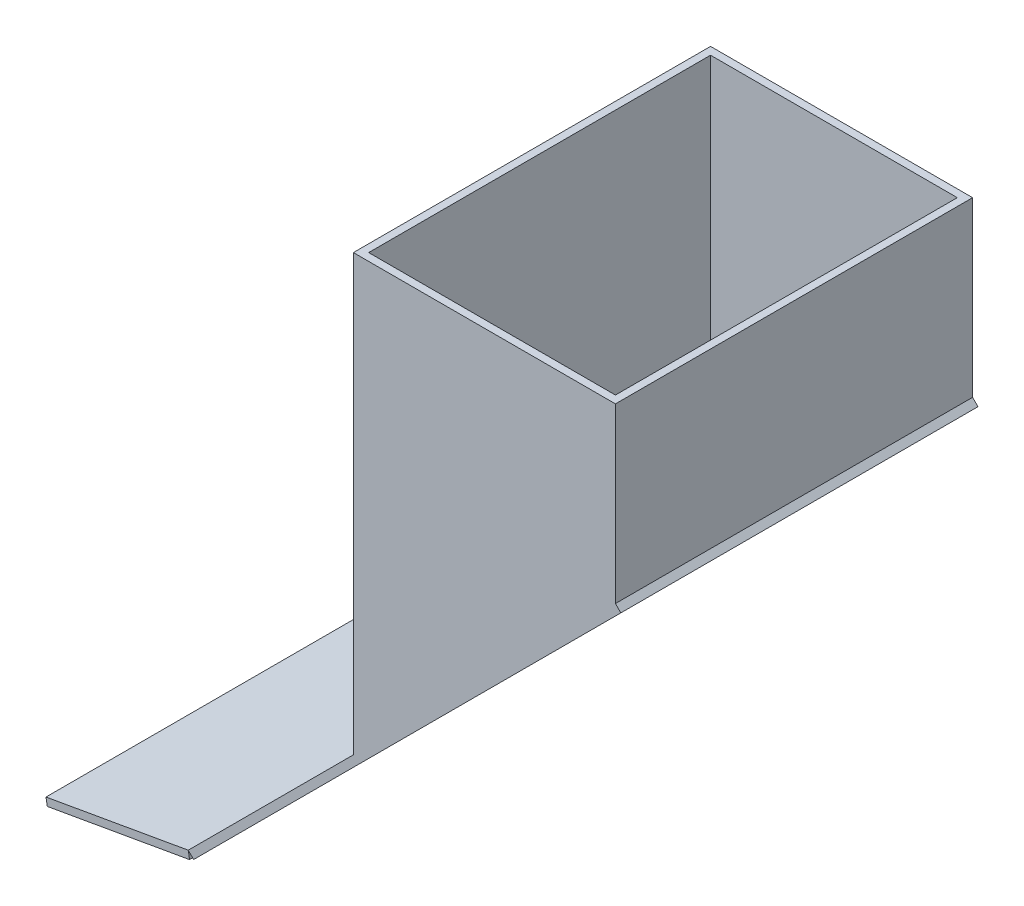
SolidWorks part; units mm, degrees
ref_plane "Front Plane" through (0, 0, 0) normal (0, 0, 1) x (1, 0, 0)
ref_plane "Top Plane" through (0, 0, 0) normal (0, 1, 0) x (1, 0, 0)
ref_plane "Right Plane" through (0, 0, 0) normal (1, 0, 0) x (0, 0, -1)
sketch "Sketch1" plane through (0, 0, 0) normal (0, 1, 0) x (1, 0, 0)
  line L1 (-102.5, 142) -> (102.5, 142)
  line L2 (-102.5, 142) -> (-102.5, -142)
  line L3 (-102.5, -142) -> (102.5, -142)
  line L4 (102.5, 142) -> (102.5, -142)
  line L5 (-102.5, 142) -> (102.5, -142) construction
  line L6 (-102.5, -142) -> (102.5, 142) construction
  line L7 (-108.85, 148.35) -> (108.85, 148.35)
  line L8 (-108.85, 148.35) -> (-108.85, -148.35)
  line L9 (-108.85, -148.35) -> (108.85, -148.35)
  line L10 (108.85, 148.35) -> (108.85, -148.35)
  line L11 (-108.85, 148.35) -> (108.85, -148.35) construction
  line L12 (-108.85, -148.35) -> (108.85, 148.35) construction
  point P0 (0, 0)
  point P5 (0, 0)
  dimension "D1" = 284
  dimension "D2" = 205
  dimension "D3" = 6.35
  dimension "D4" = 6.35
sketch3d "3DSketch1"
  line L0 (102.5, 0, 0) -> (102.5, -150, 0) construction
  line L1 (102.5, 0, -142) -> (102.5, 0, 142) construction
  line L2 (102.5, -150, 102.7398) -> (102.5, -150, -102.7398) construction
  dimension "D1" = 150
ref_plane "Base Plane" through (126.25, -126.25, 0) normal (-0.7071, 0.7071, 0) x (0, 0, -1)
extrude "Boss-Extrude1" add sketch "Sketch1" against normal up to surface (150 mm away) up to plane "Base Plane"
sketch "Sketch3" plane through (126.25, -126.25, 0) normal (-0.7071, 0.7071, 0) x (0, 0, -1)
  line L0 (-148.35, 332.4816) -> (148.35, 332.4816) construction
  line L1 (148.35, 526.4816) -> (-148.35, 526.4816)
  line L2 (148.35, 526.4816) -> (148.35, 24.6073)
  line L3 (148.35, 24.6073) -> (-148.35, 24.6073)
  line L4 (-148.35, 526.4816) -> (-148.35, 24.6073)
  dimension "D1" = 194
extrude "Boss-Extrude2" add sketch "Sketch3" against normal blind 6.35
sketch "Sketch4" plane through (0, 0, 0) normal (0, 0, 1) x (1, 0, 0)
  line L0 (-108.85, -361.35) -> (-102.5, -355)
  line L1 (-108.85, -293) -> (-102.5, -293)
  line L2 (-102.5, -355) -> (-102.5, 0) construction
  line L3 (-108.85, -361.35) -> (-108.85, -293)
  line L4 (-108.85, -361.35) -> (-108.85, 0) construction
  line L5 (-102.5, -293) -> (-102.5, -355)
  line L6 (206.1628, -46.3372) -> (46.3372, -206.1628) construction
  dimension "D2" = 62
extrude "Cut-Extrude1" cut sketch "Sketch4" against normal up to surface and the other way up to surface up to face at (0, -126.25, -142) other way up to face at (0, -126.25, 142)
sketch "Sketch5" plane through (0, 0, 0) normal (0, 0, 1) x (1, 0, 0)
  line L0 (-246.0287, -498.5287) -> (-244.926, -504.7822)
  line L1 (-246.0287, -498.5287) -> (-364.2056, -519.3665)
  line L2 (-244.926, -504.7822) -> (-363.103, -525.62)
  line L3 (-364.2056, -519.3665) -> (-363.103, -525.62)
  line L4 (163.185, 0) -> (-163.185, 0) construction
  dimension "D1" = 10
  dimension "D2" = 6.35
  dimension "D3" = 120
extrude "Boss-Extrude3" add sketch "Sketch5" against normal up to surface and the other way up to surface separate body up to face at (-53.461, -236.384, -148.35) other way up to face at (-53.461, -236.384, 148.35)
sketch "Sketch6" plane through (0, 0, 0) normal (0, 0, 1) x (1, 0, 0)
  line L8 (-108.85, -249.5) -> (-102.5, -249.5)
  line L9 (-108.85, -249.5) -> (-108.85, -269.5)
  line L10 (-108.85, -269.5) -> (-102.5, -269.5)
  line L11 (-102.5, -249.5) -> (-102.5, -269.5)
  line L12 (-102.5, -293) -> (-102.5, -355) construction
  line L13 (-108.85, -206) -> (-102.5, -206)
  line L14 (-108.85, -206) -> (-108.85, -226)
  line L15 (-108.85, -226) -> (-102.5, -226)
  line L16 (-102.5, -206) -> (-102.5, -226)
  line L17 (-108.85, -293) -> (-102.5, -293) construction
  line L18 (-108.85, -361.35) -> (-108.85, -293) construction
  point P5 (-105.675, -249.5)
  dimension "D1" = 20
  dimension "D2" = 43.5
  dimension "D4" = 20
  dimension "D5" = 43.5
extrude "Cut-Extrude2" cut sketch "Sketch6" against normal mid plane 45
equation "\"Frisbee Width\"=274"
equation "\"D1@Sketch1\"=\"Frisbee Width\"+10"
equation "\"Wall Thickness\"= 6.35"
equation "\"D3@Sketch1\"=\"Wall Thickness\""
equation "\"D4@Sketch1\"=\"Wall Thickness\""
equation "\"D1@Boss-Extrude2\"=\"Wall Thickness\""
equation "\"D1@Sketch3\"=\"Frisbee Width\"-80"
equation "\"D2@Sketch5\"=\"Wall Thickness\""
equation "\"D2@Sketch4\"=85-23"
